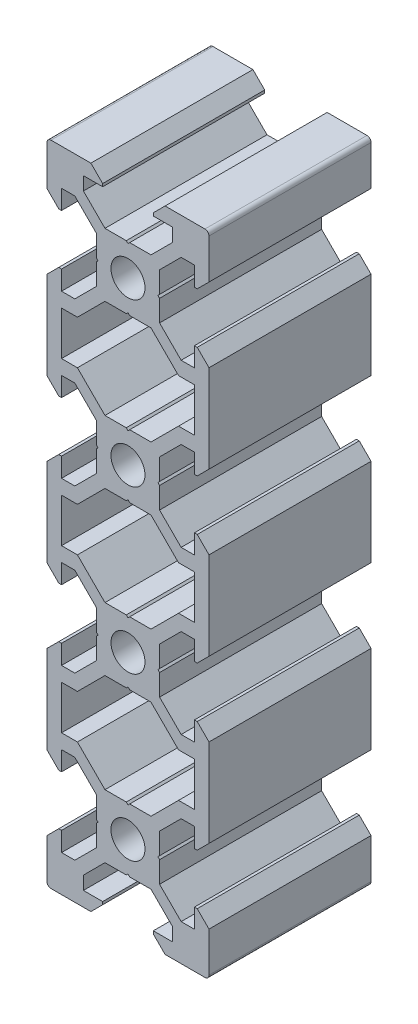
SolidWorks part; units mm, degrees
ref_plane "Plan de face" through (0, 0, 0) normal (0, 0, 1) x (1, 0, 0)
ref_plane "Plan de dessus" through (0, 0, 0) normal (0, 1, 0) x (1, 0, 0)
ref_plane "Plan de droite" through (0, 0, 0) normal (1, 0, 0) x (0, 0, -1)
ref_axis "Axe" through (0, 0, -13.782) along (0, 0, 1)
sketch "Esquisse1" plane through (0, 0, 0) normal (0, 0, 1) x (1, 0, 0)
  line L0 (0, 27.6392) -> (0, -27.6392) construction
  line L1 (-33.6074, 0) -> (33.6074, 0) construction
  line L2 (0, 0) -> (-22.2114, 22.2114) construction
  line L3 (-9.5, 10) -> (-4.58, 10)
  line L4 (-4.58, 10) -> (-3.125, 8.545)
  line L5 (-3.125, 8.545) -> (-3.125, 8.2)
  line L6 (-3.125, 8.2) -> (-5.5, 8.2)
  line L7 (-2.8393, 3.9) -> (-5.5, 6.5607)
  line L8 (-2.8393, 3.9) -> (-0.21, 3.9)
  line L9 (-5.5, 6.5607) -> (-5.5, 8.2)
  line L10 (0, 3.69) -> (0, 2.1)
  line L11 (-3.9, 2.8393) -> (-6.5607, 5.5)
  line L12 (-8.545, 3.125) -> (-8.2, 3.125)
  line L13 (-8.2, 3.125) -> (-8.2, 5.5)
  line L14 (-6.5607, 5.5) -> (-8.2, 5.5)
  line L15 (-10, 4.58) -> (-8.545, 3.125)
  line L16 (-10, 9.5) -> (-10, 4.58)
  line L17 (-0.21, 3.9) -> (0, 3.69)
  line L18 (-3.9, 2.8393) -> (-3.9, 0.21)
  line L19 (-6.2393, -12.7) -> (-8.2, -12.7)
  line L20 (-3.9, 0.21) -> (-3.69, 0)
  line L21 (-0.21, -3.9) -> (0, -3.69)
  line L22 (0, -3.69) -> (0, -2.1)
  line L23 (-6.5607, -5.5) -> (-8.2, -5.5)
  line L24 (-2.8393, -3.9) -> (-0.21, -3.9)
  line L25 (-8.545, -3.125) -> (-8.2, -3.125)
  line L26 (-10, -4.58) -> (-8.545, -3.125)
  line L27 (-8.2, -3.125) -> (-8.2, -5.5)
  line L28 (-2.8393, -3.9) -> (-6.2393, -7.3)
  line L29 (-3.9, -2.8393) -> (-6.5607, -5.5)
  line L30 (-3.9, -2.8393) -> (-3.9, -0.21)
  line L31 (-3.9, -0.21) -> (-3.69, 0)
  line L32 (-6.2393, -7.3) -> (-8.2, -7.3)
  line L33 (-8.2, -7.3) -> (-8.2, -12.7)
  line L34 (-8.2, -10) -> (-10, -10) construction
  line L35 (-10, -15.42) -> (-10, -4.58)
  line L36 (-3.9, -19.79) -> (-3.69, -20)
  line L37 (-3.9, -17.1607) -> (-3.9, -19.79)
  line L38 (-3.9, -17.1607) -> (-6.5607, -14.5)
  line L39 (-2.8393, -16.1) -> (-6.2393, -12.7)
  line L40 (-8.2, -16.875) -> (-8.2, -14.5)
  line L41 (-10, -15.42) -> (-8.545, -16.875)
  line L42 (-8.545, -16.875) -> (-8.2, -16.875)
  line L43 (-2.8393, -16.1) -> (-0.21, -16.1)
  line L44 (-6.5607, -14.5) -> (-8.2, -14.5)
  line L45 (0, -16.31) -> (0, -17.9)
  line L46 (-0.21, -16.1) -> (0, -16.31)
  line L47 (-8.2, -30) -> (-10, -30) construction
  line L48 (-3.69, -20) -> (0, -20) construction
  line L49 (-0.21, -23.9) -> (0, -23.69)
  line L50 (0, -23.69) -> (0, -22.1)
  line L51 (-6.5607, -25.5) -> (-8.2, -25.5)
  line L52 (-2.8393, -23.9) -> (-0.21, -23.9)
  line L53 (-8.545, -23.125) -> (-8.2, -23.125)
  line L54 (-10, -24.58) -> (-8.545, -23.125)
  line L55 (-8.2, -23.125) -> (-8.2, -25.5)
  line L56 (-2.8393, -23.9) -> (-6.2393, -27.3)
  line L57 (-3.9, -22.8393) -> (-6.5607, -25.5)
  line L58 (-3.9, -22.8393) -> (-3.9, -20.21)
  line L59 (-3.9, -20.21) -> (-3.69, -20)
  line L60 (-10, -24.58) -> (-10, -35.42)
  line L61 (-8.2, -32.7) -> (-8.2, -27.3)
  line L62 (-3.69, -40) -> (0, -40) construction
  line L63 (-8.2, -50) -> (-10, -50) construction
  line L64 (0, -60) -> (-22.2114, -82.2114) construction
  line L65 (-33.6074, -60) -> (33.6074, -60) construction
  line L66 (0, -87.6392) -> (0, -32.3608) construction
  line L67 (-6.2393, -32.7) -> (-8.2, -32.7)
  line L68 (-3.9, -39.79) -> (-3.69, -40)
  line L69 (-3.9, -37.1607) -> (-3.9, -39.79)
  line L70 (-3.9, -37.1607) -> (-6.5607, -34.5)
  line L71 (-2.8393, -36.1) -> (-6.2393, -32.7)
  line L72 (-8.2, -36.875) -> (-8.2, -34.5)
  line L73 (-10, -35.42) -> (-8.545, -36.875)
  line L74 (-8.545, -36.875) -> (-8.2, -36.875)
  line L75 (-6.2393, -27.3) -> (-8.2, -27.3)
  line L76 (-2.8393, -36.1) -> (-0.21, -36.1)
  line L77 (-6.5607, -34.5) -> (-8.2, -34.5)
  line L78 (0, -36.31) -> (0, -37.9)
  line L79 (-0.21, -36.1) -> (0, -36.31)
  line L80 (-0.21, -43.9) -> (0, -43.69)
  line L81 (0, -43.69) -> (0, -42.1)
  line L82 (-6.5607, -45.5) -> (-8.2, -45.5)
  line L83 (-2.8393, -43.9) -> (-0.21, -43.9)
  line L84 (-8.545, -43.125) -> (-8.2, -43.125)
  line L85 (-10, -44.58) -> (-8.545, -43.125)
  line L86 (-8.2, -43.125) -> (-8.2, -45.5)
  line L87 (-2.8393, -43.9) -> (-6.2393, -47.3)
  line L88 (-3.9, -42.8393) -> (-6.5607, -45.5)
  line L89 (-3.9, -42.8393) -> (-3.9, -40.21)
  line L90 (-3.9, -40.21) -> (-3.69, -40)
  line L91 (-10, -44.58) -> (-10, -55.42)
  line L92 (-8.2, -52.7) -> (-8.2, -47.3)
  line L93 (-6.2393, -52.7) -> (-8.2, -52.7)
  line L94 (-3.9, -59.79) -> (-3.69, -60)
  line L95 (-3.9, -57.1607) -> (-3.9, -59.79)
  line L96 (-3.9, -57.1607) -> (-6.5607, -54.5)
  line L97 (-2.8393, -56.1) -> (-6.2393, -52.7)
  line L98 (-8.2, -56.875) -> (-8.2, -54.5)
  line L99 (-10, -55.42) -> (-8.545, -56.875)
  line L100 (-8.545, -56.875) -> (-8.2, -56.875)
  line L101 (-2.8393, -56.1) -> (-0.21, -56.1)
  line L102 (-6.5607, -54.5) -> (-8.2, -54.5)
  line L103 (0, -56.31) -> (0, -57.9)
  line L104 (-0.21, -56.1) -> (0, -56.31)
  line L105 (-3.9, -60.21) -> (-3.69, -60)
  line L106 (-6.2393, -47.3) -> (-8.2, -47.3)
  line L107 (-3.9, -62.8393) -> (-3.9, -60.21)
  line L108 (-0.21, -63.9) -> (0, -63.69)
  line L109 (-10, -69.5) -> (-10, -64.58)
  line L110 (-10, -64.58) -> (-8.545, -63.125)
  line L111 (-6.5607, -65.5) -> (-8.2, -65.5)
  line L112 (-8.2, -63.125) -> (-8.2, -65.5)
  line L113 (-8.545, -63.125) -> (-8.2, -63.125)
  line L114 (-3.9, -62.8393) -> (-6.5607, -65.5)
  line L115 (0, -63.69) -> (0, -62.1)
  line L116 (-5.5, -66.5607) -> (-5.5, -68.2)
  line L117 (-2.8393, -63.9) -> (-0.21, -63.9)
  line L118 (-2.8393, -63.9) -> (-5.5, -66.5607)
  line L119 (-3.125, -68.2) -> (-5.5, -68.2)
  line L120 (-3.125, -68.545) -> (-3.125, -68.2)
  line L121 (-4.58, -70) -> (-3.125, -68.545)
  line L122 (-9.5, -70) -> (-4.58, -70)
  arc A0 (0, -2.1) -> (0, 2.1) centre (0, 0) cw
  arc A1 (-9.5, 10) -> (-10, 9.5) centre (-9.5, 9.5) ccw
  arc A2 (0, -42.1) -> (0, -37.9) centre (0, -40) cw
  arc A3 (-9.5, -70) -> (-10, -69.5) centre (-9.5, -69.5) cw
  arc A4 (0, -17.9) -> (0, -22.1) centre (0, -20) ccw
  arc A5 (0, -57.9) -> (0, -62.1) centre (0, -60) ccw
  point P4 (0, 0)
  point P7 (0, 0)
  point P30 (-10, 10)
  point P60 (0, -20)
  point P61 (0, 0)
  point P146 (-10, -70)
  dimension "D5" = 11
  dimension "D2" = 2.1
  dimension "D3" = 6.25
  dimension "D10" = 0.5
  dimension "D4" = 9.16
  dimension "D6" = 1.5
  dimension "D7" = 1.8
  dimension "D8" = 4.3
  dimension "D9" = 20
  dimension "D11" = 0.42
  dimension "D12" = 10
  dimension "D13" = 1.8
extrude "Boss.-Extru.1" add sketch "Esquisse1" along normal blind 20
sketch "Esquisse3" plane through (0, 0, 20) normal (0, 0, 1) x (1, 0, 0)
  line L0 (0, 0) -> (-9.8536, 9.8536) construction
  line L1 (-8.2, 8.2) -> (-8.2, 6.57)
  line L2 (-8.2, 6.57) -> (-7.54, 6.57)
  line L3 (-7.54, 6.57) -> (-6.57, 7.54)
  line L4 (-8.2, 3.125) -> (-8.2, 5.5) construction
  line L5 (-6.57, 8.2) -> (-6.57, 7.54)
  line L6 (-8.2, 8.2) -> (-6.57, 8.2)
  line L7 (-5.5, 6.5607) -> (-5.5, 8.2) construction
  line L8 (-10, -30) -> (6.918, -30) construction
  line L9 (-10, -24.58) -> (-10, -35.42) construction
  line L10 (-8.2, -68.2) -> (-6.57, -68.2)
  line L11 (-6.57, -68.2) -> (-6.57, -67.54)
  line L12 (-7.54, -66.57) -> (-6.57, -67.54)
  line L13 (-8.2, -66.57) -> (-7.54, -66.57)
  line L14 (-8.2, -68.2) -> (-8.2, -66.57)
  arc A0 (-9.5, 10) -> (-10, 9.5) centre (-9.5, 9.5) ccw construction
  point P13 (-7.055, 7.055)
  point P14 (-6.57, 7.87)
  point P26 (-7.055, -67.055)
  dimension "D1" = 1.07
extrude "Enlèv. mat.-Extru.1" [suppressed] cut sketch "Esquisse3" against normal through all
mirror "Symétrie1" about plane through (0, 3.69, 20) normal (-1, 0, 0) of "Enlèv. mat.-Extru.1", "Boss.-Extru.1"
